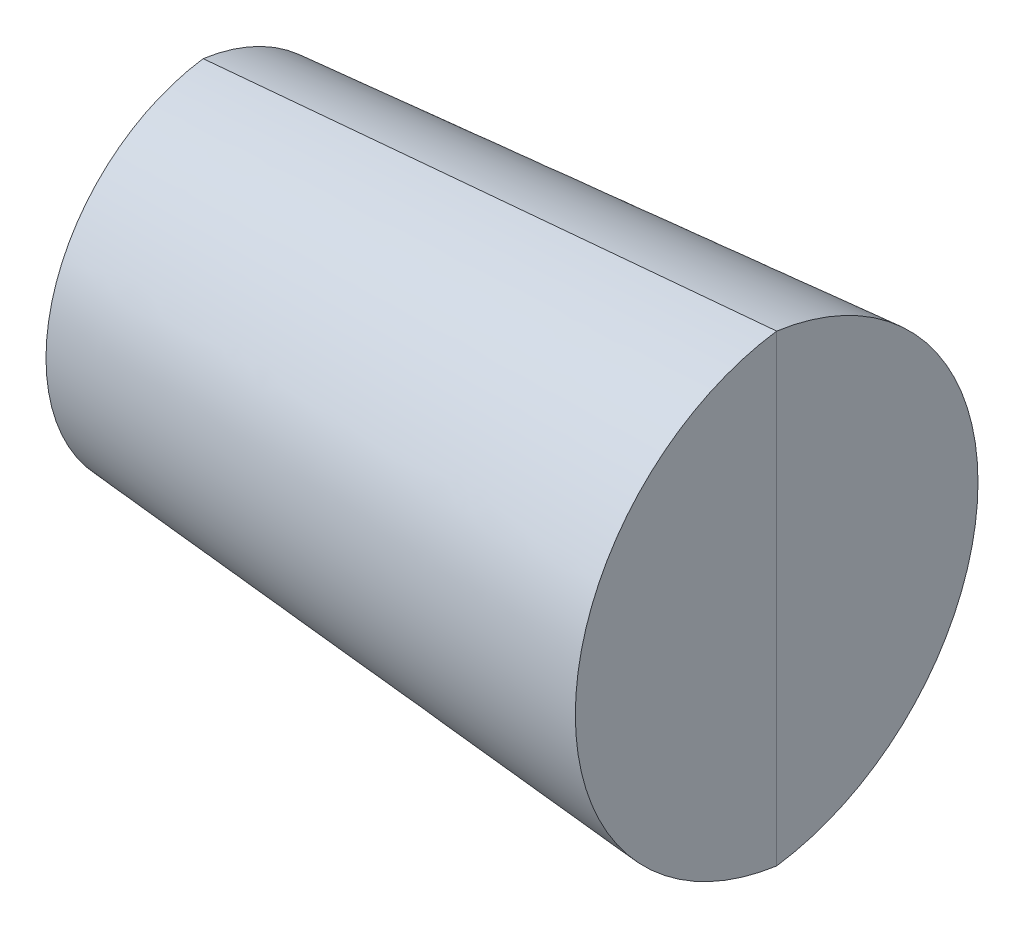
SolidWorks part; units mm, degrees
ref_plane "Front" through (0, 0, 0) normal (0, 0, 1) x (1, 0, 0)
ref_plane "Top" through (0, 0, 0) normal (0, 1, 0) x (1, 0, 0)
ref_plane "Right" through (0, 0, 0) normal (1, 0, 0) x (0, 0, -1)
sketch "Sketch1" plane through (0, 0, 0) normal (1, 0, 0) x (0, 0, -1)
  line L0 (0, -50) -> (0, 50)
  line L1 (0, 50) -> (64.1525, 59.016) construction
  line L2 (0, 50) -> (72.4006, 50) construction
  arc A0 (0, 50) -> (0, -50) centre (7.027, 0) ccw
  point P4 (0, 0)
  dimension "D2" = 8
  dimension "D1" = 100
ref_plane "Plane1" through (158.61, 0, 0) normal (1, 0, 0) x (0, 0, -1)
sketch "Sketch2" plane through (158.61, 0, 0) normal (1, 0, 0) x (0, 0, -1)
  line L0 (0, -64.055) -> (0, 64.055)
  line L3 (0, 64.055) -> (46.9346, 64.055) construction
  line L4 (0, 64.055) -> (53.0623, 71.5124) construction
  arc A0 (0, 64.055) -> (0, -64.055) centre (9.0023, 0) ccw
  point P4 (0, 0)
  dimension "D1" = 128.11
  dimension "D2" = 8
loft "Loft1" add profiles "Sketch2", "Sketch1" connector at (158.61, -64.055, 0) connector at (0, -50, 0)
mirror "Mirror3" about plane through (0, 0, 0) normal (0, 0, -1) of bodies 101
